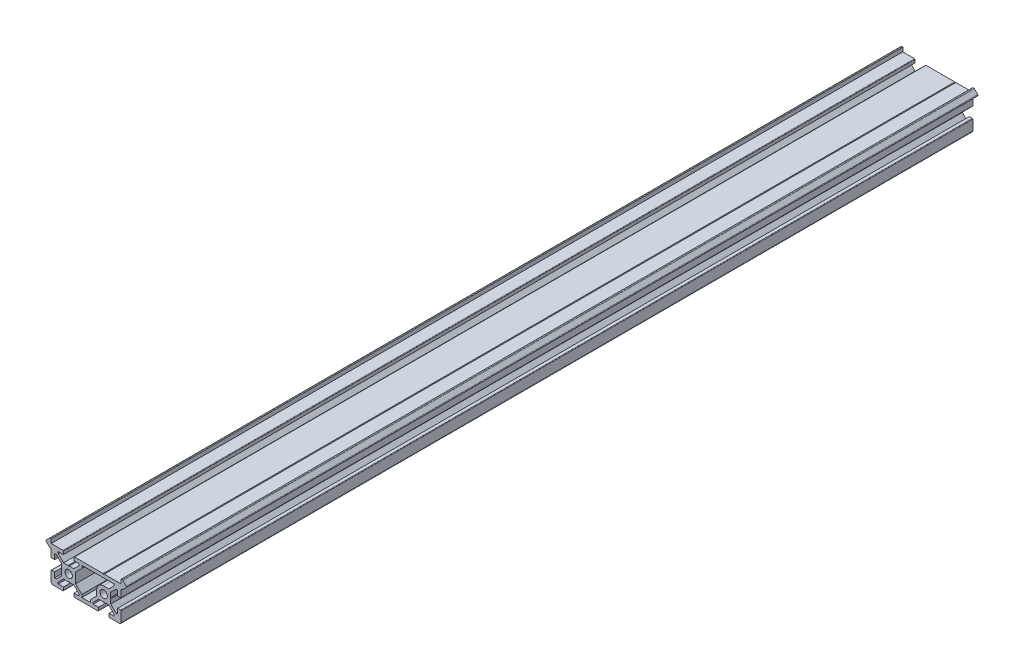
SolidWorks part; units mm, degrees
ref_plane "Front Plane" through (0, 0, 0) normal (0, 0, 1) x (1, 0, 0)
ref_plane "Top Plane" through (0, 0, 0) normal (0, 1, 0) x (1, 0, 0)
ref_plane "Right Plane" through (0, 0, 0) normal (1, 0, 0) x (0, 0, -1)
sketch "Model" plane through (0, 0, 0) normal (0, 0, 1) x (1, 0, 0)
  line L0 (0, 0) -> (0, 76.2) construction
  line L1 (0, 0) -> (101.6, 0) construction
  line L2 (0, 76.2) -> (101.6, 76.2) construction
  line L3 (101.6, 0) -> (101.6, 76.2) construction
  line L4 (28.7715, 48.1056) -> (30.6465, 49.9806)
  line L5 (31.5929, 50.127) -> (31.5929, 47.752)
  line L6 (31.5929, 44.877) -> (31.5929, 41.052)
  line L7 (31.5929, 34.452) -> (31.5929, 28.752)
  line L8 (33.5929, 31.752) -> (33.5929, 34.752)
  line L9 (33.5929, 40.752) -> (33.5929, 43.752)
  line L10 (35.5929, 29.752) -> (35.5929, 30.6914)
  line L11 (35.5929, 44.8127) -> (35.5929, 45.752)
  line L12 (37.5929, 40.6914) -> (37.5929, 38.052)
  line L13 (37.5929, 37.452) -> (37.5929, 34.8127)
  line L14 (38.5929, 28.052) -> (38.5929, 29.752)
  line L15 (38.5929, 45.752) -> (38.5929, 47.452)
  line L16 (32.5929, 27.752) -> (38.2929, 27.752)
  line L17 (44.8929, 27.752) -> (58.2929, 27.752)
  line L18 (64.8929, 27.752) -> (70.5929, 27.752)
  line L19 (37.5929, 38.052) -> (37.8929, 37.752)
  line L20 (41.5929, 34.052) -> (41.8929, 33.752)
  line L21 (30.6465, 45.5235) -> (28.7715, 47.3985)
  line L22 (41.8929, 41.752) -> (41.5929, 41.452)
  line L23 (37.8929, 37.752) -> (37.5929, 37.452)
  line L24 (67.5929, 29.752) -> (64.5929, 29.752)
  line L25 (58.5929, 29.752) -> (55.5929, 29.752)
  line L26 (54.0929, 29.752) -> (49.0929, 29.752)
  line L27 (47.5929, 29.752) -> (44.5929, 29.752)
  line L28 (38.5929, 29.752) -> (35.5929, 29.752)
  line L29 (34.5323, 43.752) -> (37.5929, 40.6914)
  line L30 (44.5323, 33.752) -> (47.5929, 30.6914)
  line L31 (44.5929, 47.452) -> (44.5929, 45.752)
  line L32 (44.5929, 29.752) -> (44.5929, 28.052)
  line L33 (47.5929, 44.8127) -> (44.5323, 41.752)
  line L34 (37.5929, 34.8127) -> (34.5323, 31.752)
  line L35 (69.5929, 31.752) -> (68.6536, 31.752)
  line L36 (34.5323, 31.752) -> (33.5929, 31.752)
  line L37 (49.0929, 31.3127) -> (45.5929, 34.8127)
  line L38 (38.6536, 41.752) -> (35.5929, 44.8127)
  line L39 (45.5929, 34.8127) -> (45.5929, 40.6914)
  line L40 (35.5929, 30.6914) -> (38.6536, 33.752)
  line L41 (45.5929, 40.6914) -> (49.0929, 44.1914)
  line L42 (38.6536, 33.752) -> (41.2929, 33.752)
  line L43 (41.8929, 33.752) -> (44.5323, 33.752)
  line L44 (58.6536, 33.752) -> (61.2929, 33.752)
  line L45 (61.8929, 33.752) -> (64.5323, 33.752)
  line L46 (41.5929, 41.452) -> (41.2929, 41.752)
  line L47 (47.5929, 45.752) -> (47.5929, 44.8127)
  line L48 (47.5929, 30.6914) -> (47.5929, 29.752)
  line L49 (41.2929, 33.752) -> (41.5929, 34.052)
  line L50 (71.2929, 34.752) -> (69.5929, 34.752)
  line L51 (33.5929, 34.752) -> (31.8929, 34.752)
  line L52 (49.0929, 29.752) -> (49.0929, 31.3127)
  line L53 (49.0929, 44.1914) -> (49.0929, 45.752)
  line L54 (61.5929, 47.452) -> (61.8929, 47.752)
  line L55 (31.8929, 40.752) -> (33.5929, 40.752)
  line L56 (69.5929, 40.752) -> (71.2929, 40.752)
  line L57 (54.0929, 31.3127) -> (54.0929, 29.752)
  line L58 (64.5323, 41.752) -> (61.4029, 41.752)
  line L59 (44.5323, 41.752) -> (41.8929, 41.752)
  line L60 (41.2929, 41.752) -> (38.6536, 41.752)
  line L61 (61.5929, 34.052) -> (61.8929, 33.752)
  line L62 (55.5929, 29.752) -> (55.5929, 30.6914)
  line L63 (33.5929, 43.752) -> (34.5323, 43.752)
  line L64 (68.6536, 43.752) -> (69.5929, 43.752)
  line L65 (57.5929, 37.942) -> (57.5929, 34.8127)
  line L66 (58.5929, 28.052) -> (58.5929, 29.752)
  line L67 (31.0929, 45.377) -> (31, 45.377)
  line L68 (72.0929, 45.377) -> (72.1858, 45.377)
  line L69 (35.5929, 45.752) -> (38.5929, 45.752)
  line L70 (44.5929, 45.752) -> (47.5929, 45.752)
  line L71 (49.0929, 45.752) -> (67.5929, 45.752)
  line L72 (64.5323, 33.752) -> (67.5929, 30.6914)
  line L73 (68.6536, 31.752) -> (65.5929, 34.8127)
  line L74 (67.5929, 44.8127) -> (64.5323, 41.752)
  line L75 (57.5929, 34.8127) -> (54.0929, 31.3127)
  line L76 (55.5929, 30.6914) -> (58.6536, 33.752)
  line L77 (65.5929, 40.6914) -> (68.6536, 43.752)
  line L78 (72.5394, 45.5235) -> (74.4144, 47.3985)
  line L79 (71.5929, 47.752) -> (61.8929, 47.752)
  line L80 (61.2929, 47.752) -> (44.8929, 47.752)
  line L81 (38.2929, 47.752) -> (31.5929, 47.752)
  line L82 (65.5929, 37.452) -> (65.2929, 37.752)
  line L83 (61.2929, 33.752) -> (61.5929, 34.052)
  line L84 (65.2929, 37.752) -> (65.5929, 38.052)
  line L85 (72.1858, 50.127) -> (71.5929, 50.127)
  line L86 (31, 50.127) -> (31.5929, 50.127)
  line L87 (64.5929, 29.752) -> (64.5929, 28.052)
  line L88 (61.2929, 47.752) -> (61.5929, 47.452)
  line L89 (65.5929, 34.8127) -> (65.5929, 37.452)
  line L90 (65.5929, 38.052) -> (65.5929, 40.6914)
  line L91 (67.5929, 45.752) -> (67.5929, 44.8127)
  line L92 (67.5929, 30.6914) -> (67.5929, 29.752)
  line L93 (69.5929, 43.752) -> (69.5929, 40.752)
  line L94 (69.5929, 34.752) -> (69.5929, 31.752)
  line L95 (71.5929, 50.127) -> (71.5929, 47.752)
  line L96 (71.5929, 28.752) -> (71.5929, 34.452)
  line L97 (71.5929, 41.052) -> (71.5929, 44.877)
  line L98 (74.4144, 48.1056) -> (72.5394, 49.9806)
  arc A0 (61.4029, 41.752) -> (57.5929, 37.942) centre (61.4029, 37.942) ccw
  circle A1 centre (61.5929, 37.752) radius 2.1
  circle A2 centre (41.5929, 37.752) radius 2.1
  arc A3 (31.5929, 28.752) -> (32.5929, 27.752) centre (32.5929, 28.752) ccw
  arc A4 (70.5929, 27.752) -> (71.5929, 28.752) centre (70.5929, 28.752) ccw
  arc A5 (31.5929, 44.877) -> (31.0929, 45.377) centre (31.0929, 44.877) ccw
  arc A6 (72.0929, 45.377) -> (71.5929, 44.877) centre (72.0929, 44.877) ccw
  arc A7 (31, 50.127) -> (30.6465, 49.9806) centre (31, 49.627) ccw
  arc A8 (28.7715, 48.1056) -> (28.7715, 47.3985) centre (29.125, 47.752) ccw
  arc A9 (30.6465, 45.5235) -> (31, 45.377) centre (31, 45.877) ccw
  arc A10 (72.5394, 49.9806) -> (72.1858, 50.127) centre (72.1858, 49.627) ccw
  arc A11 (74.4144, 47.3985) -> (74.4144, 48.1056) centre (74.0608, 47.752) ccw
  arc A12 (72.1858, 45.377) -> (72.5394, 45.5235) centre (72.1858, 45.877) ccw
  arc A13 (31.8929, 34.752) -> (31.5929, 34.452) centre (31.8929, 34.452) ccw
  arc A14 (44.8929, 47.752) -> (44.5929, 47.452) centre (44.8929, 47.452) ccw
  arc A15 (38.5929, 47.452) -> (38.2929, 47.752) centre (38.2929, 47.452) ccw
  arc A16 (31.5929, 41.052) -> (31.8929, 40.752) centre (31.8929, 41.052) ccw
  arc A17 (38.2929, 27.752) -> (38.5929, 28.052) centre (38.2929, 28.052) ccw
  arc A18 (44.5929, 28.052) -> (44.8929, 27.752) centre (44.8929, 28.052) ccw
  arc A19 (58.2929, 27.752) -> (58.5929, 28.052) centre (58.2929, 28.052) ccw
  arc A20 (64.5929, 28.052) -> (64.8929, 27.752) centre (64.8929, 28.052) ccw
  arc A21 (71.5929, 34.452) -> (71.2929, 34.752) centre (71.2929, 34.452) ccw
  arc A22 (71.2929, 40.752) -> (71.5929, 41.052) centre (71.2929, 41.052) ccw
extrude "Boss-Extrude1" add sketch "Model" along normal offset from surface (486.36 mm away) 20 offset beyond the face yes
ref_plane "Plane1" through (51.5929, 0, 0) normal (-1, 0, 0) x (0, 0, 1)
